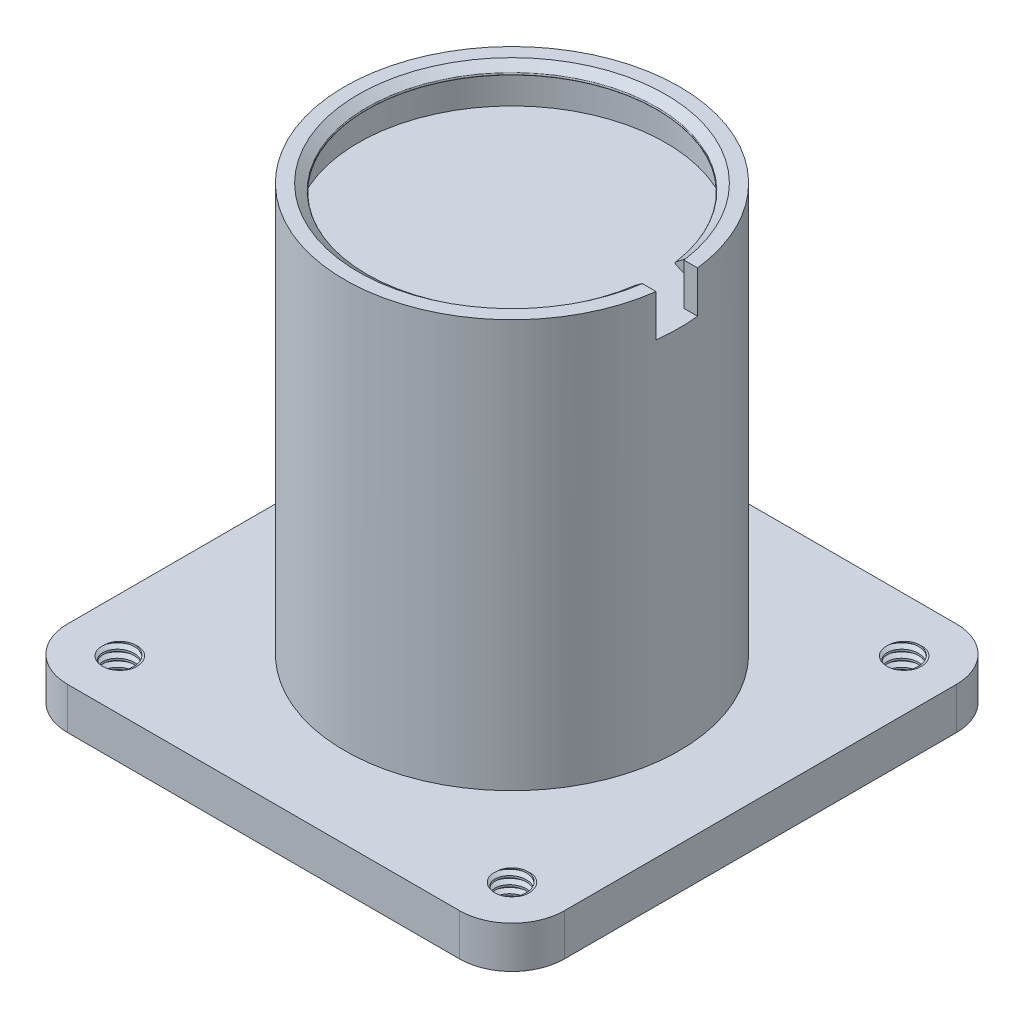
SolidWorks part; units mm, degrees
ref_plane "Front Plane" through (0, 0, 0) normal (0, 0, 1) x (1, 0, 0)
ref_plane "Top Plane" through (0, 0, 0) normal (0, 1, 0) x (1, 0, 0)
ref_plane "Right Plane" through (0, 0, 0) normal (1, 0, 0) x (0, 0, -1)
sketch "Sketch1" plane through (0, 0, 0) normal (0, 1, 0) x (1, 0, 0)
  line L1 (-37.5, -47.5) -> (37.5, -47.5)
  line L2 (-47.5, -37.5) -> (-47.5, 37.5)
  line L3 (-37.5, 47.5) -> (37.5, 47.5)
  line L4 (47.5, -37.5) -> (47.5, 37.5)
  line L5 (-47.5, -47.5) -> (47.5, 47.5) construction
  line L6 (-47.5, 47.5) -> (47.5, -47.5) construction
  circle A0 centre (0, 0) radius 29.4
  circle A1 centre (0, 0) radius 32
  arc A2 (37.5, -47.5) -> (47.5, -37.5) centre (37.5, -37.5) ccw
  arc A3 (-37.5, -47.5) -> (-47.5, -37.5) centre (-37.5, -37.5) cw
  arc A4 (37.5, 47.5) -> (47.5, 37.5) centre (37.5, 37.5) cw
  arc A5 (-47.5, 37.5) -> (-37.5, 47.5) centre (-37.5, 37.5) cw
  circle A6 centre (-37.5, 37.5) radius 3
  circle A7 centre (37.5, 37.5) radius 3
  circle A8 centre (-37.5, -37.5) radius 3
  circle A9 centre (37.5, -37.5) radius 3
  point P0 (0, 0)
  dimension "D3" = 58.8
  dimension "D4" = 64
  dimension "D5" = 10
  dimension "D6" = 6
  dimension "D1" = 95
  dimension "D2" = 95
extrude "Boss-Extrude2" add sketch "Sketch1" along normal blind 8 contours A5 L3 A4 L4 A2 L1 A3 L2
sketch "Sketch2" plane through (0, 8, 0) normal (0, 1, 0) x (1, 0, 0)
  line L4 (-47.5, 37.5) -> (-47.5, -37.5)
  line L5 (-37.5, -47.5) -> (37.5, -47.5)
  line L6 (47.5, -37.5) -> (47.5, 37.5)
  line L7 (37.5, 47.5) -> (-37.5, 47.5)
  line L8 (-47.5, 37.5) -> (-47.5, -37.5)
  line L9 (-37.5, -47.5) -> (37.5, -47.5)
  line L10 (47.5, -37.5) -> (47.5, 37.5)
  line L11 (37.5, 47.5) -> (-37.5, 47.5)
  circle A0 centre (0, 0) radius 29.4 construction
  circle A1 centre (0, 0) radius 32 construction
  circle A2 centre (0, 0) radius 29.4
  circle A3 centre (0, 0) radius 32
  arc A4 (-47.5, -37.5) -> (-37.5, -47.5) centre (-37.5, -37.5) ccw
  arc A5 (37.5, -47.5) -> (47.5, -37.5) centre (37.5, -37.5) ccw
  arc A6 (47.5, 37.5) -> (37.5, 47.5) centre (37.5, 37.5) ccw
  arc A7 (-37.5, 47.5) -> (-47.5, 37.5) centre (-37.5, 37.5) ccw
  arc A8 (-47.5, -37.5) -> (-37.5, -47.5) centre (-37.5, -37.5) ccw
  arc A9 (37.5, -47.5) -> (47.5, -37.5) centre (37.5, -37.5) ccw
  arc A10 (47.5, 37.5) -> (37.5, 47.5) centre (37.5, 37.5) ccw
  arc A11 (-37.5, 47.5) -> (-47.5, 37.5) centre (-37.5, 37.5) ccw
  dimension "D1" = 0
extrude "Boss-Extrude3" add sketch "Sketch2" along normal blind 70 contours A2
sketch "Sketch3" plane through (0, 8, 0) normal (0, 1, 0) x (1, 0, 0)
  line L4 (-47.5, 37.5) -> (-47.5, -37.5)
  line L5 (-37.5, -47.5) -> (37.5, -47.5)
  line L6 (47.5, -37.5) -> (47.5, 37.5)
  line L7 (37.5, 47.5) -> (-37.5, 47.5)
  line L8 (-47.5, 37.5) -> (-47.5, -37.5)
  line L9 (-37.5, -47.5) -> (37.5, -47.5)
  line L10 (47.5, -37.5) -> (47.5, 37.5)
  line L11 (37.5, 47.5) -> (-37.5, 47.5)
  circle A0 centre (0, 0) radius 32 construction
  circle A1 centre (0, 0) radius 29.4 construction
  circle A2 centre (0, 0) radius 32
  circle A3 centre (0, 0) radius 29.4
  arc A4 (-47.5, -37.5) -> (-37.5, -47.5) centre (-37.5, -37.5) ccw
  arc A5 (37.5, -47.5) -> (47.5, -37.5) centre (37.5, -37.5) ccw
  arc A6 (47.5, 37.5) -> (37.5, 47.5) centre (37.5, 37.5) ccw
  arc A7 (-37.5, 47.5) -> (-47.5, 37.5) centre (-37.5, 37.5) ccw
  arc A8 (-47.5, -37.5) -> (-37.5, -47.5) centre (-37.5, -37.5) ccw
  arc A9 (37.5, -47.5) -> (47.5, -37.5) centre (37.5, -37.5) ccw
  arc A10 (47.5, 37.5) -> (37.5, 47.5) centre (37.5, 37.5) ccw
  arc A11 (-37.5, 47.5) -> (-47.5, 37.5) centre (-37.5, 37.5) ccw
  circle M11 centre (0, 0) radius 29.4
  dimension "D1" = 0
extrude "Boss-Extrude4" add sketch "Sketch3" along normal blind 78 contours A2 M11 region at (-31.0949, 8, 0)
sketch "Sketch4" plane through (0, 86, 0) normal (0, 1, 0) x (1, 0, 0)
  line L2 (29.1655, 3.7058) -> (31.7847, 3.7058)
  line L3 (29.1023, -4.173) -> (31.7267, -4.173)
  circle A0 centre (0, 0) radius 29.4 construction
  circle A1 centre (0, 0) radius 32 construction
  arc A2 (31.9507, -1.7753) -> (31.9268, 2.1639) centre (0, 0) ccw
  arc A3 (29.3465, -1.7723) -> (29.3205, 2.1602) centre (0, 0) ccw
  circle A4 centre (0, 0) radius 32 construction
  circle A5 centre (0, 0) radius 29.4 construction
  arc A6 (31.7267, -4.173) -> (31.7847, 3.7058) centre (0, 0) ccw
  arc A7 (29.1023, -4.173) -> (29.1655, 3.7058) centre (0, 0) ccw
  point P0 (29.3205, 2.1602)
  point P1 (31.9268, 2.1639)
  point P2 (29.1655, 3.7058)
  point P4 (31.9507, -1.7753)
  point P7 (29.3465, -1.7723)
  point P12 (31.7847, 3.7058)
  point P13 (31.7267, -4.173)
  point P16 (29.1023, -4.173)
extrude "Cut-Extrude2" cut sketch "Sketch4" against normal blind 8 contours A6 L2 A7 L3
sketch "Sketch5" plane through (0, 8, 0) normal (0, 1, 0) x (1, 0, 0)
  line L4 (-47.5, 37.5) -> (-47.5, -37.5)
  line L5 (-37.5, -47.5) -> (37.5, -47.5)
  line L6 (47.5, -37.5) -> (47.5, 37.5)
  line L7 (37.5, 47.5) -> (-37.5, 47.5)
  line L8 (-47.5, 37.5) -> (-47.5, -37.5)
  line L9 (-37.5, -47.5) -> (37.5, -47.5)
  line L10 (47.5, -37.5) -> (47.5, 37.5)
  line L11 (37.5, 47.5) -> (-37.5, 47.5)
  circle A0 centre (-37.5, -37.5) radius 3 construction
  circle A1 centre (37.5, -37.5) radius 3 construction
  circle A2 centre (37.5, 37.5) radius 3 construction
  circle A3 centre (-37.5, 37.5) radius 3 construction
  arc A4 (-47.5, -37.5) -> (-37.5, -47.5) centre (-37.5, -37.5) ccw
  arc A5 (37.5, -47.5) -> (47.5, -37.5) centre (37.5, -37.5) ccw
  arc A6 (47.5, 37.5) -> (37.5, 47.5) centre (37.5, 37.5) ccw
  arc A7 (-37.5, 47.5) -> (-47.5, 37.5) centre (-37.5, 37.5) ccw
  arc A8 (-47.5, -37.5) -> (-37.5, -47.5) centre (-37.5, -37.5) ccw
  arc A9 (37.5, -47.5) -> (47.5, -37.5) centre (37.5, -37.5) ccw
  arc A10 (47.5, 37.5) -> (37.5, 47.5) centre (37.5, 37.5) ccw
  arc A11 (-37.5, 47.5) -> (-47.5, 37.5) centre (-37.5, 37.5) ccw
  circle A12 centre (-37.5, -37.5) radius 3
  circle A13 centre (37.5, -37.5) radius 3
  circle A14 centre (37.5, 37.5) radius 3
  circle A15 centre (-37.5, 37.5) radius 3
  dimension "D1" = 0
extrude "Cut-Extrude3" cut sketch "Sketch5" against normal blind 8 contours A12 | A15 | A13 | A14 region at (-37.5, 8, 37.5) region at (-37.5, 8, -37.5)
thread "Thread1" pitch 1.5 method cut trim with start face yes trim with end face yes profile "Thread Profile1" start angle 0, offset 1.5, length 10, pitch 1.5, diameter 6
ref_plane "Plane1" through (-40.5, 9.5, -37.5) normal (0, 0, 1) x (-1, 0, 0)
sketch "Thread Profile1" plane through (-40.5, 9.5, -37.5) normal (0, 0, 1) x (-1, 0, 0)
  line L0 (0, 0) -> (0, 1.5) construction
  line L1 (0, 0) -> (0.8119, 0.4687)
  line L2 (0.8119, 0.4687) -> (0.8119, 0.6562)
  line L3 (0.8119, 0.6562) -> (0, 1.125)
  line L4 (0.8119, 0.5625) -> (0, 0.5625) construction
  line L11 (0, 0) -> (0, 1.125)
  point P2 (0, 0)
  dimension "Pitch" = 1.5
  dimension "Profile_Angle" = 60
  dimension "Profile_Land" = 0.1875
  dimension "Profile_Height" = 0.8119
thread "Thread3" pitch 1.5 method cut trim with start face yes trim with end face yes profile "Thread Profile3" start angle 0, offset 1.5, length 10, pitch 1.5, diameter 6
ref_plane "Plane3" through (34.5, 9.5, -37.5) normal (0, 0, 1) x (-1, 0, 0)
sketch "Thread Profile3" plane through (34.5, 9.5, -37.5) normal (0, 0, 1) x (-1, 0, 0)
  line L0 (0, 0) -> (0, 1.5) construction
  line L1 (0, 0) -> (0.8119, 0.4687)
  line L2 (0.8119, 0.4687) -> (0.8119, 0.6562)
  line L3 (0.8119, 0.6562) -> (0, 1.125)
  line L4 (0.8119, 0.5625) -> (0, 0.5625) construction
  line L11 (0, 0) -> (0, 1.125)
  point P2 (0, 0)
  dimension "Pitch" = 1.5
  dimension "Profile_Angle" = 60
  dimension "Profile_Land" = 0.1875
  dimension "Profile_Height" = 0.8119
thread "Thread4" pitch 1.5 method cut trim with start face yes trim with end face yes profile "Thread Profile4" start angle 0, offset 1.5, length 10, pitch 1.5, diameter 6
ref_plane "Plane4" through (34.5, 9.5, 37.5) normal (0, 0, 1) x (-1, 0, 0)
sketch "Thread Profile4" plane through (34.5, 9.5, 37.5) normal (0, 0, 1) x (-1, 0, 0)
  line L0 (0, 0) -> (0, 1.5) construction
  line L1 (0, 0) -> (0.8119, 0.4687)
  line L2 (0.8119, 0.4687) -> (0.8119, 0.6562)
  line L3 (0.8119, 0.6562) -> (0, 1.125)
  line L4 (0.8119, 0.5625) -> (0, 0.5625) construction
  line L11 (0, 0) -> (0, 1.125)
  point P2 (0, 0)
  dimension "Pitch" = 1.5
  dimension "Profile_Angle" = 60
  dimension "Profile_Land" = 0.1875
  dimension "Profile_Height" = 0.8119
thread "Thread5" pitch 1.5 method cut trim with start face yes trim with end face yes profile "Thread Profile5" start angle 0, offset 1.5, length 10, pitch 1.5, diameter 6
ref_plane "Plane5" through (-40.5, 9.5, 37.5) normal (0, 0, 1) x (-1, 0, 0)
sketch "Thread Profile5" plane through (-40.5, 9.5, 37.5) normal (0, 0, 1) x (-1, 0, 0)
  line L0 (0, 0) -> (0, 1.5) construction
  line L1 (0, 0) -> (0.8119, 0.4687)
  line L2 (0.8119, 0.4687) -> (0.8119, 0.6562)
  line L3 (0.8119, 0.6562) -> (0, 1.125)
  line L4 (0.8119, 0.5625) -> (0, 0.5625) construction
  line L11 (0, 0) -> (0, 1.125)
  point P2 (0, 0)
  dimension "Pitch" = 1.5
  dimension "Profile_Angle" = 60
  dimension "Profile_Land" = 0.1875
  dimension "Profile_Height" = 0.8119
sketch "Sketch6" plane through (0, 0, 0) normal (0, 0, 1) x (1, 0, 0)
  line L0 (-29.4, 86) -> (-29.4, 78) construction
  line L1 (-29.4, 86) -> (-29.4, 83.3124)
  line L3 (-29.4, 86) -> (-27.7057, 84.7293)
  line L5 (-27.7682, 84.2814) -> (-29.4, 83.3124)
  arc A0 (-27.7682, 84.2814) -> (-27.7057, 84.7293) centre (-27.9215, 84.5311) ccw
  point P2 (-29.4, 84.5)
  point P5 (-27.4, 84.5)
  dimension "D1" = 8
  dimension "D2" = 6.5
  dimension "D3" = 2
sketch "Sketch7" plane through (0, 0, 0) normal (0, 0, 1) x (1, 0, 0)
  line L0 (0, 0) -> (0, 15.4194)
  line L1 (-37.5, 0) -> (37.5, 0) construction
revolve "Revolve1" add sketch "Sketch6" angle 172 about L0 other way angle 172
